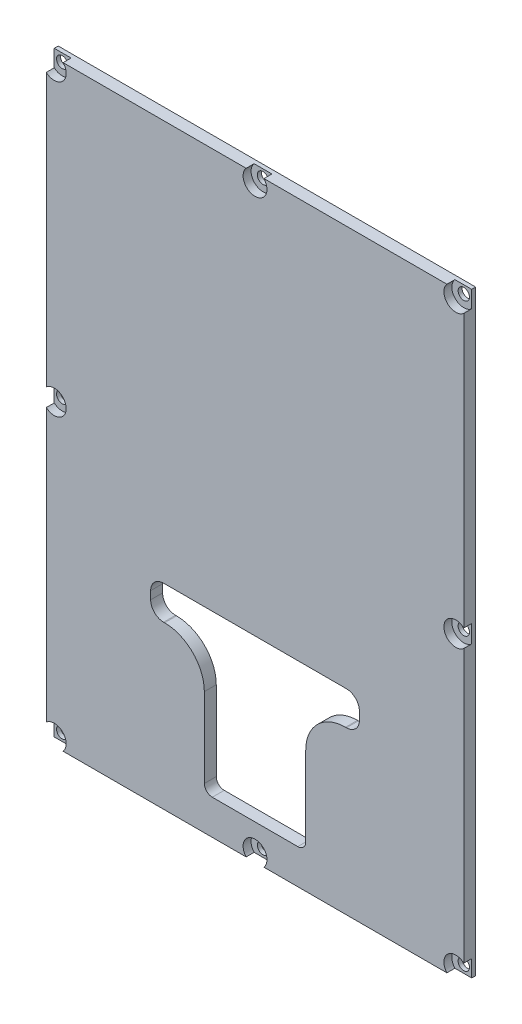
SolidWorks part; units mm, degrees
ref_plane "Спереди" through (0, 0, 0) normal (0, 0, 1) x (1, 0, 0)
ref_plane "Сверху" through (0, 0, 0) normal (0, 1, 0) x (1, 0, 0)
ref_plane "Справа" through (0, 0, 0) normal (1, 0, 0) x (0, 0, -1)
sketch "Эскиз1" plane through (0, 0, 0) normal (0, 0, 1) x (1, 0, 0)
  line L1 (-52.5, -75) -> (52.5, -75)
  line L2 (-52.5, -75) -> (-52.5, 75)
  line L3 (-52.5, 75) -> (52.5, 75)
  line L4 (52.5, -75) -> (52.5, 75)
  line L5 (-52.5, -75) -> (52.5, 75) construction
  line L6 (-52.5, 75) -> (52.5, -75) construction
  point P0 (0, 0)
  dimension "D1" = 105
  dimension "D2" = 150
extrude "Бобышка-Вытянуть1" add sketch "Эскиз1" along normal blind 3
sketch "Эскиз2" plane through (0, 0, 0) normal (0, 0, -1) x (-1, 0, 0)
  line L0 (-26.25, -29) -> (-26.25, -31)
  line L1 (-23, -34.25) -> (-22.75, -34.25)
  line L2 (-12.75, -44.25) -> (-12.75, -64.25)
  line L3 (-10.75, -66.25) -> (10.75, -66.25)
  line L4 (12.75, -64.25) -> (12.75, -44.25)
  line L5 (22.75, -34.25) -> (23, -34.25)
  line L6 (26.25, -31) -> (26.25, -29)
  line L7 (23, -25.75) -> (-23, -25.75)
  line L8 (-52.5, -75) -> (-52.5, 75) construction
  line L9 (52.5, 75) -> (52.5, -75) construction
  line L10 (52.5, -75) -> (-52.5, -75) construction
  arc A0 (22.75, -34.25) -> (12.75, -44.25) centre (22.75, -44.25) ccw
  arc A1 (-12.75, -44.25) -> (-22.75, -34.25) centre (-22.75, -44.25) ccw
  arc A2 (23, -34.25) -> (26.25, -31) centre (23, -31) ccw
  arc A3 (26.25, -29) -> (23, -25.75) centre (23, -29) ccw
  arc A4 (-23, -34.25) -> (-26.25, -31) centre (-23, -31) cw
  arc A5 (-23, -25.75) -> (-26.25, -29) centre (-23, -29) ccw
  arc A6 (12.75, -64.25) -> (10.75, -66.25) centre (10.75, -64.25) cw
  arc A7 (-10.75, -66.25) -> (-12.75, -64.25) centre (-10.75, -64.25) cw
  point P16 (12.75, -34.25)
  point P21 (26.25, -34.25)
  point P24 (26.25, -25.75)
  point P31 (12.75, -66.25)
  point P34 (-12.75, -66.25)
  dimension "D7" = 10
  dimension "D8" = 3.25
  dimension "D9" = 2
  dimension "D1" = 26.25
  dimension "D2" = 26.25
  dimension "D3" = 49.25
  dimension "D4" = 8.5
  dimension "D5" = 25.5
  dimension "D6" = 32
extrude "Вырез-Вытянуть1" cut sketch "Эскиз2" against normal blind 10
sketch "Эскиз3" plane through (0, 0, 3) normal (0, 0, 1) x (1, 0, 0)
  line L0 (-50.5, -940.9285) -> (-50.5, 49059.0715) construction
  line L1 (50.5, -944.6511) -> (50.5, 49055.3489) construction
  line L2 (-1032.3277, 73) -> (48967.6723, 73) construction
  line L3 (-1028.801, -73) -> (48971.199, -73) construction
  line L4 (-52.5, -75) -> (52.5, -75) construction
  line L6 (-52.5, 75) -> (-52.5, -75) construction
  line L7 (52.5, -75) -> (52.5, 75) construction
  line L8 (52.5, 75) -> (-52.5, 75) construction
  line L9 (0, -925) -> (0, 49075) construction
  line L10 (-1052.5, 0) -> (48947.5, 0) construction
  circle A0 centre (-50.5, 73) radius 3
  circle A1 centre (0, 73) radius 3
  circle A2 centre (50.5, 73) radius 3
  circle A3 centre (50.5, 0) radius 3
  circle A4 centre (50.5, -73) radius 3
  circle A5 centre (0, -73) radius 3
  circle A6 centre (-50.5, -73) radius 3
  circle A7 centre (-50.5, 0) radius 3
  point P19 (0, 75)
  point P22 (-52.5, 0)
  dimension "D5" = 6
  dimension "D1" = 2
  dimension "D2" = 2
  dimension "D3" = 2
  dimension "D4" = 2
extrude "Вырез-Вытянуть2" cut sketch "Эскиз3" against normal blind 2
sketch "Эскиз4" plane through (0, 0, 1) normal (0, 0, 1) x (1, 0, 0)
  circle A0 centre (-50.5, 73) radius 1.425
  circle A1 centre (0, 73) radius 1.425
  circle A2 centre (50.5, 73) radius 1.425
  circle A3 centre (50.5, 0) radius 1.425
  circle A4 centre (50.5, -73) radius 1.425
  circle A5 centre (0, -73) radius 1.425
  circle A6 centre (-50.5, -73) radius 1.425
  circle A7 centre (-50.5, 0) radius 1.425
  dimension "D1" = 2.85
extrude "Вырез-Вытянуть3" cut sketch "Эскиз4" against normal blind 2
